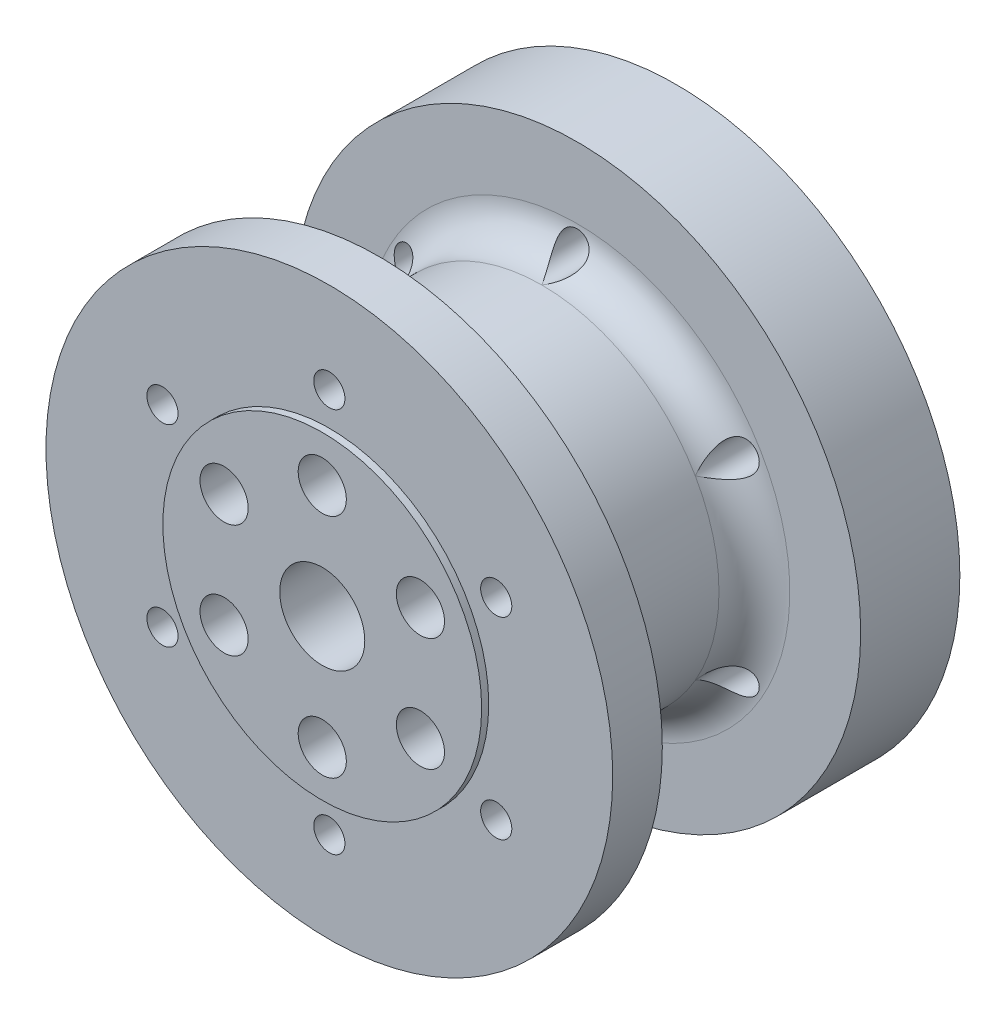
SolidWorks part; units mm, degrees
material "Nylon - impressão"
ref_plane "Plano frontal" through (0, 0, 0) normal (0, 0, 1) x (1, 0, 0)
ref_plane "Plano superior" through (0, 0, 0) normal (0, 1, 0) x (1, 0, 0)
ref_plane "Plano direito" through (0, 0, 0) normal (1, 0, 0) x (0, 0, -1)
sketch "Esboço1" plane through (0, 0, 0) normal (1, 0, 0) x (0, 0, -1)
  line L0 (1.5, 11.25) -> (1.5, 20)
  line L1 (1.5, 20) -> (5, 20)
  line L2 (5, 20) -> (5, 12.5)
  line L3 (5, 12.5) -> (19, 12.5)
  line L4 (19, 12.5) -> (19, 20)
  line L5 (19, 20) -> (27, 20)
  line L6 (27, 20) -> (27, 3)
  line L9 (27, 3) -> (0, 3)
  line L10 (0, 3) -> (0, 11.25)
  line L11 (0, 11.25) -> (1.5, 11.25)
  line L12 (0, 0) -> (24.3309, 0) construction
  line L14 (0, 11.25) -> (-3, 11.25) construction
  line L15 (0, 11.25) -> (0, 3) construction
  line L16 (0, 3) -> (-3, 3) construction
  line L17 (-3, 11.25) -> (-3, 3) construction
  dimension "D1" = 25
  dimension "D2" = 6
  dimension "D3" = 14
  dimension "D4" = 22.5
  dimension "D5" = 30
  dimension "D6" = 5
  dimension "D7" = 1.5
  dimension "D8" = 3
  dimension "D9" = 40
revolve "Revolução1" add sketch "Esboço1" angle 360 about L12
sketch "Esboço2" plane through (0, 0, -27) normal (0, 0, -1) x (-1, 0, 0)
  circle A0 centre (0, 0) radius 8 construction
  circle A1 centre (0, 8) radius 1.6
  circle A2 centre (6.9282, 4) radius 1.6
  circle A3 centre (6.9282, -4) radius 1.6
  circle A4 centre (0, -8) radius 1.6
  circle A5 centre (-6.9282, -4) radius 1.6
  circle A6 centre (-6.9282, 4) radius 1.6
  point P17 (0, 0)
  dimension "D1" = 16
  dimension "D2" = 3.2
  dimension "D3" = 6
extrude "Corte-extrusão1" cut sketch "Esboço2" against normal through all
hole_wizard "Rebaixo para SHCS M31" positions "Esboço3" profile "Esboço4" counterbore size "M3" standard "Ansi Metric" end condition through all
sketch "Esboço3" plane through (0, 0, -27) normal (0, 0, -1) x (-1, 0, 0)
  point P0 (0, 8)
  point P3 (-6.9282, 4)
  point P6 (-6.9282, -4)
  point P9 (0, -8)
  point P12 (6.9282, -4)
  point P15 (6.9282, 4)
sketch "Esboço4" plane through (0, 8, -27) normal (1, 0, 0) x (0, 1, 0)
  line L0 (0, 0) -> (0, 27)
  line L1 (0, 27) -> (1.7, 27)
  line L3 (1.7, 27) -> (1.7, 4)
  line L4 (3.25, 4) -> (1.7, 4)
  line L5 (3.25, 4) -> (3.25, 0.025)
  line L6 (3.25, 0.025) -> (3.275, 0)
  line L7 (3.275, 0) -> (0, 0)
  line L8 (-3.25, 0.025) -> (-3.275, 0) construction
  line L11 (0, -6.35) -> (0, 107.95) construction
  dimension "Thru Hole Dia." = 3.4
  dimension "Thru Hole Depth" = 27
  dimension "C'Bore Dia." = 6.5
  dimension "C'Bore Depth" = 4
  dimension "Near C'Sink Dia." = 6.55
  dimension "Near C'Sink Angle" = 90
sketch "Esboço5" plane through (0, 0, -27) normal (0, 0, -1) x (-1, 0, 0)
  circle A0 centre (0, 0) radius 11.275
extrude "Corte-extrusão2" cut sketch "Esboço5" against normal up to surface (4 mm away) up to face at (5.2282, 4, -23)
fillet "Filete1" radius 2.5 2 edges at (12.5, 0, -19) (12.5, 0, -5)
sketch "Esboço6" plane through (0, 0, -27) normal (0, 0, -1) x (-1, 0, 0)
  line L0 (0, -13.6) -> (0, 0) construction
  circle A0 centre (0, 0) radius 12.5 construction
  circle A1 centre (0, 0) radius 12.5 construction
  circle A2 centre (0, -13.6) radius 1.1
  circle A3 centre (-11.7779, -6.8) radius 1.1
  circle A4 centre (-11.7779, 6.8) radius 1.1
  circle A5 centre (0, 13.6) radius 1.1
  circle A6 centre (11.7779, 6.8) radius 1.1
  circle A7 centre (11.7779, -6.8) radius 1.1
  point P22 (0, 0)
  dimension "D1" = 2.2
  dimension "D2" = 6
extrude "Corte-extrusão3" cut sketch "Esboço6" against normal through all both and the other way through all
sketch "Esboço7" plane through (0, 0, -27) normal (0, 0, -1) x (-1, 0, 0)
  circle A0 centre (0, 0) radius 16.5
  dimension "D1" = 33
extrude "Corte-extrusão4" cut sketch "Esboço7" against normal up to surface (4 mm away) up to face at (-8.6282, 4, -23)
sketch "Esboço10" plane through (0, 0, -23) normal (0, 0, -1) x (-1, 0, 0)
  circle A0 centre (0, 0) radius 3 construction
  circle A1 centre (0, 0) radius 3
  circle A2 centre (0, 0) radius 5
  circle M7 centre (0, 0) radius 3
  dimension "D1" = 10
extrude "Ressalto-extrusão3" add sketch "Esboço10" along normal offset from surface (7 mm away) 3 contours A2 M7 region at (4.8586, 0, -23) up to face at (-16.5, 0, -27) offset beyond the face yes
sketch "Esboço11" plane through (0, 0, -27) normal (0, 0, -1) x (-1, 0, 0)
  circle A0 centre (0, 0) radius 16.5 construction
  circle A1 centre (0, 0) radius 20
  circle A2 centre (0, 0) radius 20
  circle A3 centre (0, 0) radius 16.5
  dimension "D1" = 0
extrude "Corte-extrusão6" cut sketch "Esboço11" against normal blind 1
sketch "Esboço12" plane through (0, 0, 0) normal (0, 0, 1) x (1, 0, 0)
  circle A1 centre (0, 0) radius 11.25
  circle A2 centre (0, 0) radius 11.25
  dimension "D1" = 0
extrude "Corte-extrusão7" cut sketch "Esboço12" against normal blind 1
